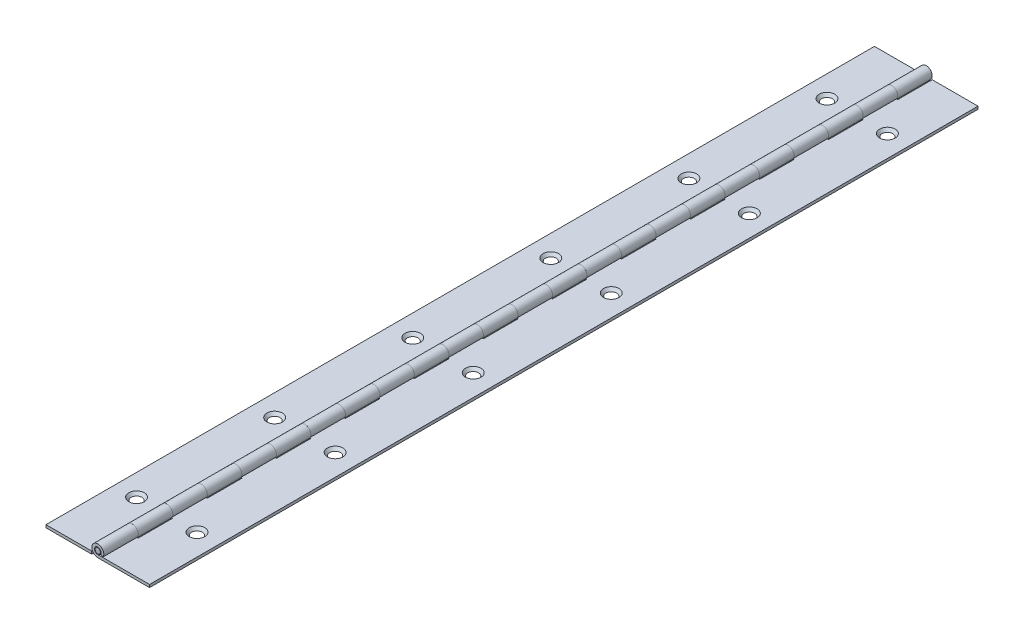
SolidWorks part; units mm, degrees
note: '?' marks a value the reader was unsure of.
ref_plane "Front Plane" through (0, 0, 0) normal (0, 0, 1) x (1, 0, 0)
ref_plane "Top Plane" through (0, 0, 0) normal (0, 1, 0) x (1, 0, 0)
ref_plane "Right Plane" through (0, 0, 0) normal (1, 0, 0) x (0, 0, -1)
sketch "Sketch1" plane through (0, 0, 0) normal (0, 0, 1) x (1, 0, 0)
  line L0 (1.8578, -1.1906) -> (19.05, -1.1906)
  line L1 (19.05, -1.1906) -> (19.05, -2.2066)
  line L2 (19.05, -2.2066) -> (0, -2.2066)
  line L3 (0, 0) -> (0, 1.1906) construction
  line L4 (-1.1906, 0) -> (-2.2066, 0) construction
  line L5 (1.0791, -0.5032) -> (1.9999, -0.9326) construction
  line L6 (-1.0791, -0.5032) -> (-1.9999, -0.9326) construction
  circle A0 centre (0, 0) radius 1.1906
  circle A1 centre (0, 0) radius 2.2066
  dimension "D4" = 4.4133
  dimension "leaf thickness" = 1.016
  dimension "open width" = 38.1
  dimension "D5" = 25
  dimension "D6" = 25
sketch "Sketch2" plane through (0, 0, 0) normal (0, 0, 1) x (1, 0, 0)
  line L0 (19.05, -1.1906) -> (19.05, -2.2066) construction
  line L1 (1.8578, -1.1906) -> (19.05, -1.1906) construction
  line L2 (1.0791, -0.5032) -> (1.9999, -0.9326) construction
  line L3 (19.05, -2.2066) -> (0, -2.2066) construction
  line L4 (19.05, -1.1906) -> (19.05, -2.2066)
  line L5 (0, -1.1906) -> (19.05, -1.1906)
  line L6 (1.0791, -0.5032) -> (1.9999, -0.9326)
  line L7 (19.05, -2.2066) -> (0, -2.2066)
  circle A0 centre (0, 0) radius 1.1906 construction
  circle A1 centre (0, 0) radius 2.2066 construction
  arc A2 (1.0791, -0.5032) -> (0, -1.1906) centre (0, 0) ccw
  arc A3 (1.9999, -0.9326) -> (0, -2.2066) centre (0, 0) ccw
extrude "Extrude1" add sketch "Sketch2" along normal mid plane 1219.2
sketch "Sketch3" plane through (0, -1.1906, 0) normal (0, 1, 0) x (1, 0, 0)
  line L0 (19.05, -609.6) -> (0, -609.6) construction
  line L1 (-2.2066, -584.2) -> (2.2066, -584.2)
  line L2 (-2.2066, -584.2) -> (-2.2066, -596.9)
  line L3 (-2.2066, -596.9) -> (2.2066, -596.9)
  line L4 (2.2066, -584.2) -> (2.2066, -596.9)
  line L7 (2.2066, -609.6) -> (2.2066, 609.6) construction
  line L8 (-2.2066, 609.6) -> (-2.2066, -609.6) construction
  dimension "D4" = 12.7
extrude "Cut-Extrude1" cut sketch "Sketch3" against normal mid plane 50.8
pattern_linear "LPattern1" count 48 spacing 25.4 along (0, 0, -1) of "Cut-Extrude1"
sketch "Sketch5" plane through (0, 0, -609.6) normal (0, 0, -1) x (-1, 0, 0)
  line L0 (-1.8578, -1.1906) -> (-19.05, -1.1906) construction
  line L1 (-19.05, -2.2066) -> (0, -2.2066) construction
  line L2 (0, -1.1906) -> (19.05, -1.1906)
  line L3 (19.05, -2.2066) -> (0, -2.2066)
  line L4 (1.0791, -0.5032) -> (1.9999, -0.9326) construction
  line L5 (1.0791, -0.5032) -> (1.9999, -0.9326)
  line L6 (19.05, -1.1906) -> (19.05, -2.2066)
  line L8 (0, 0) -> (0, -2.2066) construction
  circle A0 centre (0, 0) radius 2.2066 construction
  arc A1 (1.9999, -0.9326) -> (0, -2.2066) centre (0, 0) ccw
  circle A2 centre (0, 0) radius 1.1906 construction
  arc A3 (1.0791, -0.5032) -> (0, -1.1906) centre (0, 0) ccw
  dimension "D1" = 38.1
extrude "Extrude2" add sketch "Sketch5" against normal blind 12.7 separate body
pattern_linear "LPattern3" count 48 spacing 25.4 along (0, 0, 1) of bodies 104
sketch "Sketch6" plane through (0, 0, -609.6) normal (0, 0, -1) x (-1, 0, 0)
  line L0 (0, -2.2066) -> (19.05, -2.2066) construction
  line L1 (19.05, -1.1906) -> (2.232, -1.1906)
  line L2 (19.05, -1.1906) -> (19.05, -2.2066)
  line L3 (19.05, -2.2066) -> (2.232, -2.2066)
  line L4 (2.232, -1.1906) -> (2.232, -2.2066)
  line L6 (19.05, -1.1906) -> (0, -1.1906) construction
  line L7 (2.2066, 1.5054) -> (2.2066, -2.5761) construction
  arc A0 (1.9999, -0.9326) -> (0, -2.2066) centre (0, 0) ccw construction
  dimension "D1" = 0.0254
extrude "Extrude5" add sketch "Sketch6" against normal blind 1219.2
sketch "Sketch10" plane through (0, -1.1906, 0) normal (0, 1, 0) x (1, 0, 0)
  line L1 (0, -2.4273) -> (0, 2.4273) construction
  line L2 (19.05, 609.6) -> (2.2066, 609.6) construction
  circle A0 centre (11.1252, 584.2) radius 2.8575
  point P2 (10.6283, 609.6)
  dimension "D3" = 25.4
  dimension "hole dia" = 5.715
  dimension "hole off center" = 11.1252
extrude "Cut-Extrude2" cut sketch "Sketch10" against normal through all draft 41
sketch "Sketch11" plane through (0, -1.1906, 0) normal (0, 1, 0) x (1, 0, 0)
  line L0 (0, -2.4273) -> (0, 2.4273) construction
  circle A0 centre (-11.1252, 584.2) radius 2.8575
  circle A1 centre (11.1252, 584.2) radius 2.8575 construction
  dimension "D1" = 11.1252
extrude "Cut-Extrude3" cut sketch "Sketch11" against normal through all draft 41
pattern_linear "LPattern4" count 24 spacing 50.8 along (0, 0, 1) of "Cut-Extrude2"
pattern_linear "LPattern5" count 24 spacing 50.8 along (0, 0, 1) of "Cut-Extrude3"
sketch "Sketch7" plane through (0, 0, 0) normal (0, 0, 1) x (1, 0, 0)
  circle A0 centre (0, 0) radius 1.1906 construction
  circle A1 centre (0, 0) radius 1.1906
extrude "Extrude4" add sketch "Sketch7" along normal mid plane 1219.2 separate body
chamfer "Chamfer1" distance 0.2381 angle 45 2 edges at (1.1906, 0, 609.6) (1.1906, 0, -609.6)
sketch "Sketch8" plane through (0, 0, 0) normal (0, 1, 0) x (1, 0, 0)
  line L0 (19.05, 0) -> (-19.05, 0) construction
  line L1 (19.05, 0) -> (0, 0) construction
  line L2 (-19.05, -609.6) -> (-19.05, 609.6) construction
  line L3 (19.05, -609.6) -> (19.05, 609.6) construction
sketch "Sketch9" plane through (0, 0, 0) normal (0, 1, 0) x (1, 0, 0)
  line L0 (2.2066, 596.9) -> (2.2066, 609.6) construction
  point P0 (-19.05, 609.6)
  point P1 (19.05, 609.6)
  point P3 (-19.05, -609.6)
  point P5 (19.05, -609.6)
  point P7 (2.2066, 596.9)
sketch "Sketch12" plane through (0, -1.1906, 0) normal (0, 1, 0) x (1, 0, 0)
  line L0 (86.36, -304.8) -> (19.05, -304.8) construction
  line L1 (-82.3465, 1030.6103) -> (265.6718, 1030.6103)
  line L2 (-82.3465, 1030.6103) -> (-82.3465, -304.8)
  line L3 (-82.3465, -304.8) -> (265.6718, -304.8)
  line L4 (265.6718, 1030.6103) -> (265.6718, -304.8)
extrude "Extrude8" cut sketch "Sketch12" against normal mid plane 17.78
ref_axis "Axis1" through (0, 0, 317.5) along (0, 0, -1)?
equation "\"D4@Sketch3\" = \"knuckle length@Sketch3\""
equation "\"D1@LPattern1\" = \"overall length@Extrude1\"/(\"knuckle length@Sketch3\"*2)"
equation "\"D1@Sketch5\" = \"open width@Sketch1\""
equation "\"D1@LPattern3\" = \"D1@LPattern1\""
equation "\"D1@Extrude4\" = \"overall length@Extrude1\""
equation "\"D3@LPattern1\" = \"knuckle length@Sketch3\"*2"
equation "\"D3@LPattern3\" = \"D3@LPattern1\""
equation "\"D1@Chamfer1\" = \"pin diameter@Sketch1\"*.1"
equation "\"D1@Extrude2\" = \"knuckle length@Sketch3\""
equation "\"D1@Extrude5\" = \"overall length@Extrude1\""
equation "\"D1@LPattern4\" = \"overall length@Extrude1\"/2"
equation "\"D1@Sketch11\" = \"hole off center@Sketch10\""
equation "\"D3@Cut-Extrude3\" = \"D3@Cut-Extrude2\""
equation "\"D1@LPattern5\" = \"D1@LPattern4\""
equation "\"D3@LPattern5\" = \"D3@LPattern4\""
